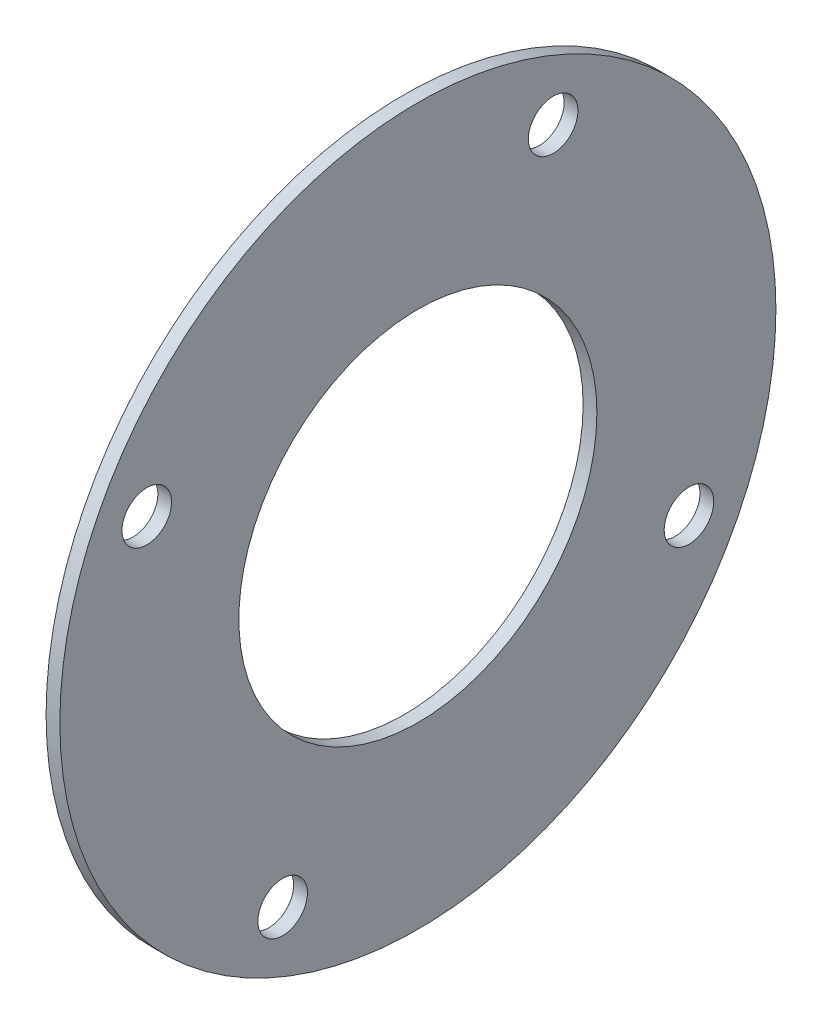
SolidWorks part; units mm, degrees
ref_plane "Спереди" through (0, 0, 0) normal (0, 0, 1) x (1, 0, 0)
ref_plane "Сверху" through (0, 0, 0) normal (0, 1, 0) x (1, 0, 0)
ref_plane "Справа" through (0, 0, 0) normal (1, 0, 0) x (0, 0, -1)
sketch "Эскиз1" plane through (0, 0, 0) normal (1, 0, 0) x (0, 0, -1)
  circle A0 centre (0, 0) radius 26
  circle A1 centre (0, 0) radius 13
  circle A2 centre (0, 0) radius 13 construction
  circle A3 centre (0, 0) radius 26 construction
extrude "Бобышка-Вытянуть1" add sketch "Эскиз1" along normal blind 1
hole_wizard "Зенковка для винта с полупотайной головкой M32" positions "Эскиз6" profile "Эскиз7" hole size "M3" standard "DIN" end condition up to next
sketch "Эскиз6" plane through (0, 0, 0) normal (-1, 0, 0) x (0, 0, 1)
  circle A0 centre (19.686, 9.8215) radius 1.8 construction
  point P0 (19.686, 9.8215)
sketch "Эскиз7" plane through (0, 9.8215, 19.686) normal (0, 1, 0) x (0, 0, 1)
  line L0 (0, 0) -> (0, 1)
  line L1 (0, 1) -> (1.8, 1)
  line L2 (1.8, 1) -> (1.8, 0)
  line L5 (1.8, 0) -> (0, 0)
  line L11 (0, -6.35) -> (0, 107.95) construction
  dimension "Диаметр сквозного отверстия" = 3.6
  dimension "Глубина сквозного отверстия" = 1
pattern_circular "Круговой массив1" count 4 over 360 about axis through (0, 0, 0) along (1, 0, 0) of "Зенковка для винта с полупотайной головкой M32"
